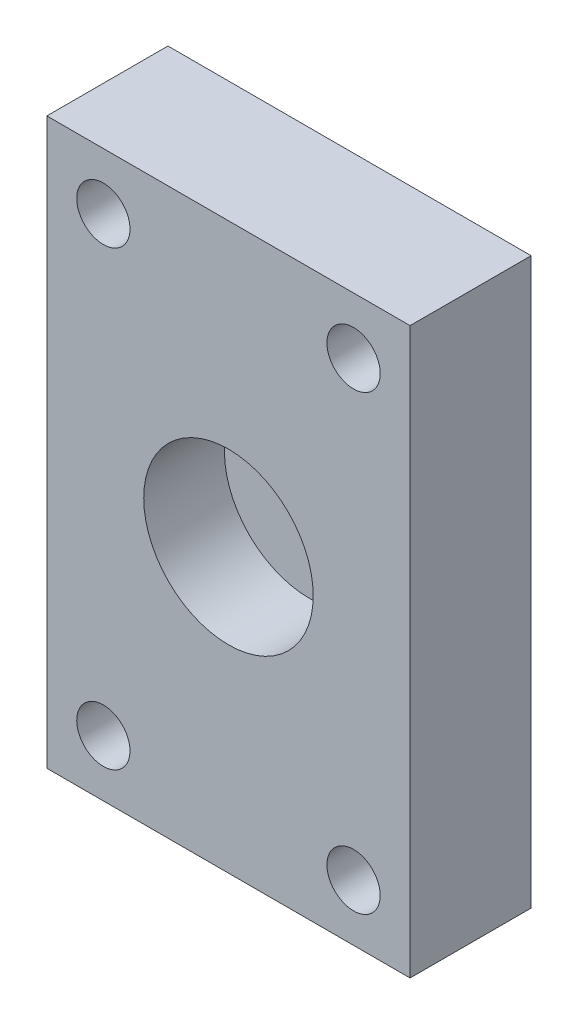
SolidWorks part; units mm, degrees
ref_plane "Piano frontale" through (0, 0, 0) normal (0, 0, 1) x (1, 0, 0)
ref_plane "Piano superiore" through (0, 0, 0) normal (0, 1, 0) x (1, 0, 0)
ref_plane "Piano destro" through (0, 0, 0) normal (1, 0, 0) x (0, 0, -1)
sketch "Schizzo1" plane through (0, 0, 0) normal (0, 0, 1) x (1, 0, 0)
  line L1 (0, 0) -> (45, 0)
  line L2 (0, 0) -> (0, 70)
  line L3 (0, 70) -> (45, 70)
  line L4 (45, 0) -> (45, 70)
  dimension "D1" = 70
  dimension "D2" = 45
extrude "Estrusione-Estrusione1" add sketch "Schizzo1" against normal blind 15
sketch "Schizzo2" plane through (0, 0, 0) normal (0, 0, 1) x (1, 0, 0)
  line L0 (22.5, 70) -> (22.5, 0) construction
  line L1 (45, 70) -> (0, 70) construction
  line L2 (0, 0) -> (45, 0) construction
  line L3 (45, 0) -> (23.1103, 0) construction
  line L4 (45, 0) -> (45, 70) construction
  line L5 (45, 35) -> (22.5, 35) construction
  line L6 (45, 7) -> (23.1103, 7) construction
  line L7 (45, 0) -> (45, 31.4323) construction
  line L8 (38, 0) -> (38, 31.4323) construction
  circle A0 centre (22.5, 35) radius 10.5
  circle A1 centre (38, 7) radius 3.3
  circle A2 centre (38, 63) radius 3.3
  circle A3 centre (7, 7) radius 3.3
  circle A4 centre (7, 63) radius 3.3
  dimension "D1" = 21
  dimension "D4" = 6.6
  dimension "D2" = 7
  dimension "D3" = 7
extrude "Taglio-Estrusione1" cut sketch "Schizzo2" against normal blind 10
